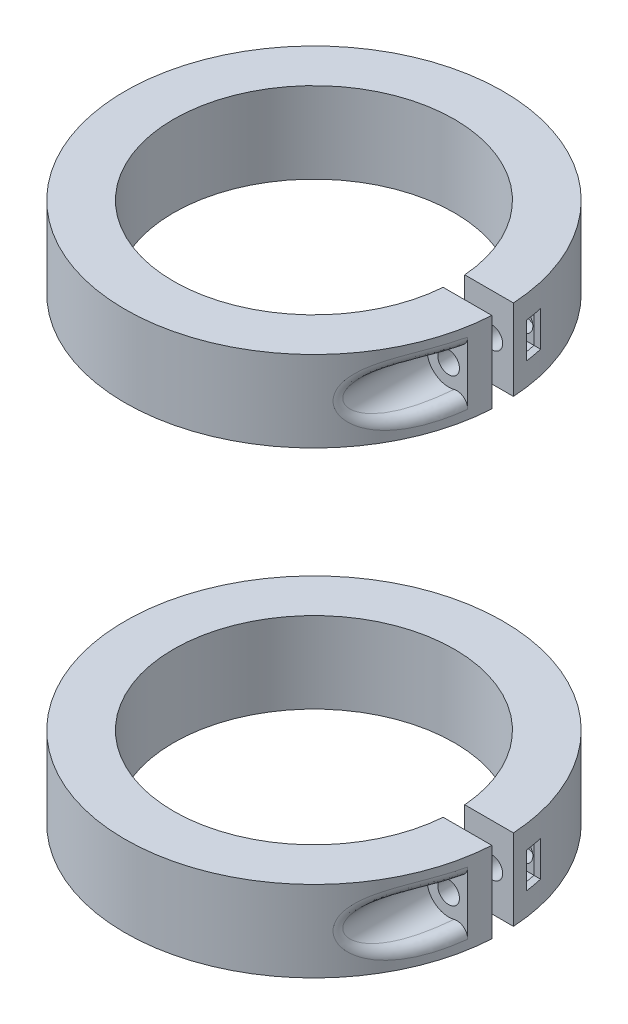
SolidWorks part; units mm, degrees
ref_plane "Front Plane" through (0, 0, 0) normal (0, 0, 1) x (1, 0, 0)
ref_plane "Top Plane" through (0, 0, 0) normal (0, 1, 0) x (1, 0, 0)
ref_plane "Right Plane" through (0, 0, 0) normal (1, 0, 0) x (0, 0, -1)
sketch "Sketch1" plane through (0, 0, 0) normal (0, 1, 0) x (1, 0, 0)
  line L0 (0, 0) -> (35, 0) construction
  line L1 (25.923, -2) -> (34.9428, -2)
  line L2 (25.923, 2) -> (34.9428, 2)
  line L3 (0, 2) -> (35, 2) construction
  line L4 (0, -2) -> (35, -2) construction
  circle A0 centre (0, 0) radius 12.5
  circle A1 centre (0, 0) radius 26
  arc A2 (34.9428, 2) -> (34.9428, -2) centre (0, 0) ccw
  point P5 (0, 0)
  point P7 (34.2649, 0)
  point P8 (35, 0)
  dimension "D1" = 52
  dimension "D2" = 25
  dimension "D3" = 70
  dimension "D4" = 2
  dimension "D5" = 2
extrude "Boss-Extrude1" add sketch "Sketch1" along normal blind 15 contours L2 A2 L1 A1 region at (30.4329, 0, 2.9895)
sketch "Sketch3" plane through (0, 0, -2) normal (0, 0, 1) x (1, 0, 0)
  line L0 (25.923, 15) -> (34.9428, 15) construction
  line L3 (34.9428, 7.5) -> (25.923, 7.5) construction
  line L4 (34.9428, 15) -> (34.9428, 0) construction
  line L5 (25.923, 15) -> (25.923, 0) construction
  line L6 (30.9428, 15) -> (30.9428, 0) construction
  line L7 (25.923, 0) -> (34.9428, 0) construction
  circle A0 centre (30.9428, 7.5) radius 2
  circle A1 centre (30.9428, 7.5) radius 4
  point P0 (30.9428, 15)
  dimension "D2" = 8
  dimension "D3" = 4
  dimension "D1" = 4
extrude "Cut-Extrude1" cut sketch "Sketch3" against normal blind 8 and the other way blind 28 contours A0 region at (30.9428, 7.5, -2)
extrude "Cut-Extrude2" cut sketch "Sketch3<3>" along normal blind 18 from offset 8
sketch "Sketch3<3>" plane through (0, 0, -2) normal (0, 0, 1) x (1, 0, 0) same geometry as "Sketch3"
fillet "Fillet1" radius 2 1 edges at (26.9465, 7.3288, 22.3358)
ref_plane "Plane1" through (35, 0, 0) normal (1, 0, 0) x (0, 0, -1)
sketch "Sketch5" plane through (35, 0, 0) normal (1, 0, 0) x (0, 0, -1)
  line L0 (10, 9.5) -> (2, 9.5) construction
  line L1 (2, 15) -> (2, 0) construction
  line L2 (10, 7.5) -> (2, 7.5) construction
  line L3 (10, 9.5) -> (10, 5.5) construction
  line L4 (2, 9.5) -> (2, 5.5) construction
  line L5 (7.6, 7.5) -> (7.6, 10.5) construction
  line L7 (7.6, 10.5) -> (5, 10.5)
  line L8 (7.6, 10.5) -> (7.6, 4.5)
  line L9 (7.6, 4.5) -> (5, 4.5)
  line L10 (5, 10.5) -> (5, 4.5)
  line L11 (7.6, 10.5) -> (5, 4.5) construction
  line L12 (7.6, 4.5) -> (5, 10.5) construction
  point P0 (5, 9.5)
  point P11 (7.6, 9.5)
  point P17 (6.3, 7.5)
  dimension "D1" = 3
  dimension "D2" = 2.6
  dimension "D3" = 3
  dimension "D4" = 6
extrude "Cut-Extrude3" cut sketch "Sketch5" against normal blind 8
chamfer "Chamfer1" distance 1 angle 15 4 edges at (34.4275, 4.5, -6.3045) (34.641, 7.5, -5) (34.4275, 10.5, -6.3045) (34.1649, 7.5, -7.6) first distance on face at (30.7076, 4.5, -6.3011) first distance on face at (30.9428, 5.5, -5) first distance on face at (30.7076, 10.5, -6.3011) first distance on face at (28.9428, 7.5, -7.6)
ref_plane "Plane2" through (0, 50, 0) normal (0, 1, 0) x (1, 0, 0)
mirror "Mirror2" about plane through (0, 50, 0) normal (0, 1, 0) of bodies 104
